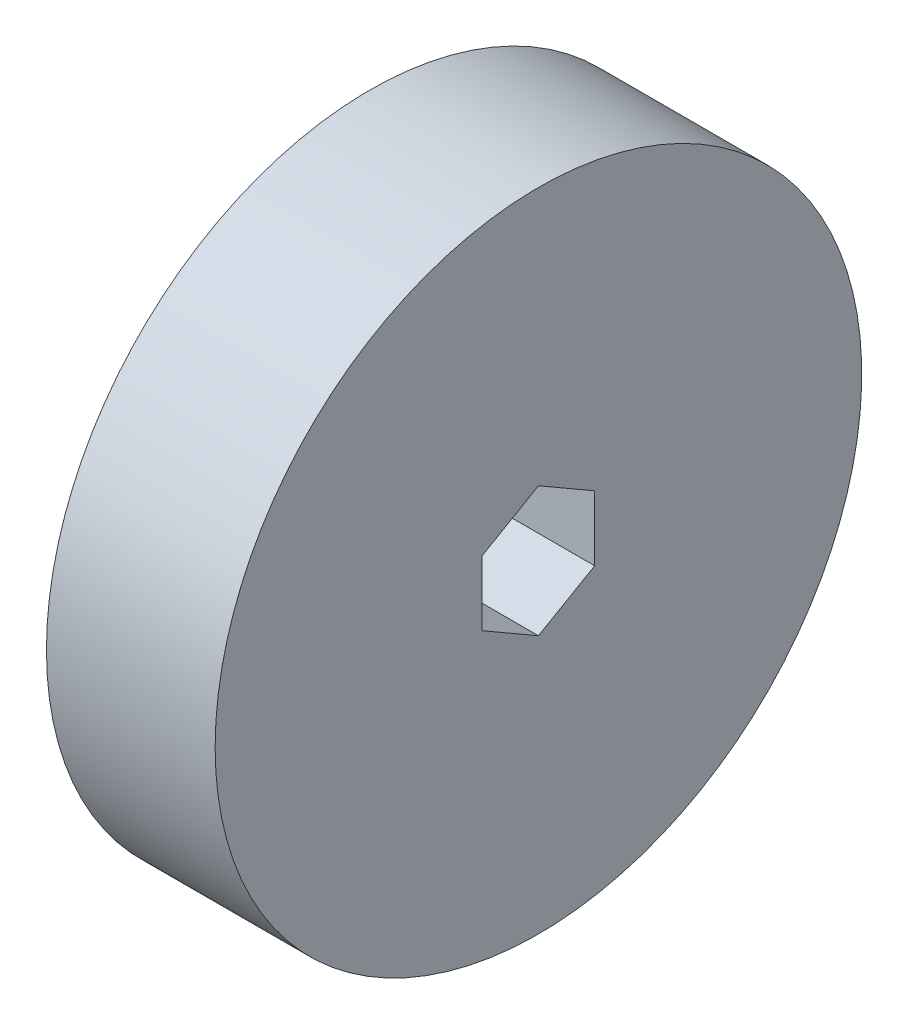
SolidWorks part; units mm, degrees
ref_plane "Front Plane" through (0, 0, 0) normal (0, 0, 1) x (1, 0, 0)
ref_plane "Top Plane" through (0, 0, 0) normal (0, 1, 0) x (1, 0, 0)
ref_plane "Right Plane" through (0, 0, 0) normal (1, 0, 0) x (0, 0, -1)
sketch "Sketch2" plane through (0, 0, 0) normal (1, 0, 0) x (0, 0, -1)
  line L1 (0, 7.3323) -> (-6.35, 3.6662)
  line L2 (-6.35, 3.6662) -> (-6.35, -3.6662)
  line L3 (-6.35, -3.6662) -> (0, -7.3323)
  line L4 (0, -7.3323) -> (6.35, -3.6662)
  line L5 (6.35, -3.6662) -> (6.35, 3.6662)
  line L6 (6.35, 3.6662) -> (0, 7.3323)
  circle A0 centre (0, 0) radius 36.5125
  circle A1 centre (0, 0) radius 6.35 construction
  dimension "D1" = 73.025
  dimension "D2" = 12.7
extrude "Boss-Extrude1" add sketch "Sketch2" along normal mid plane 19.05
